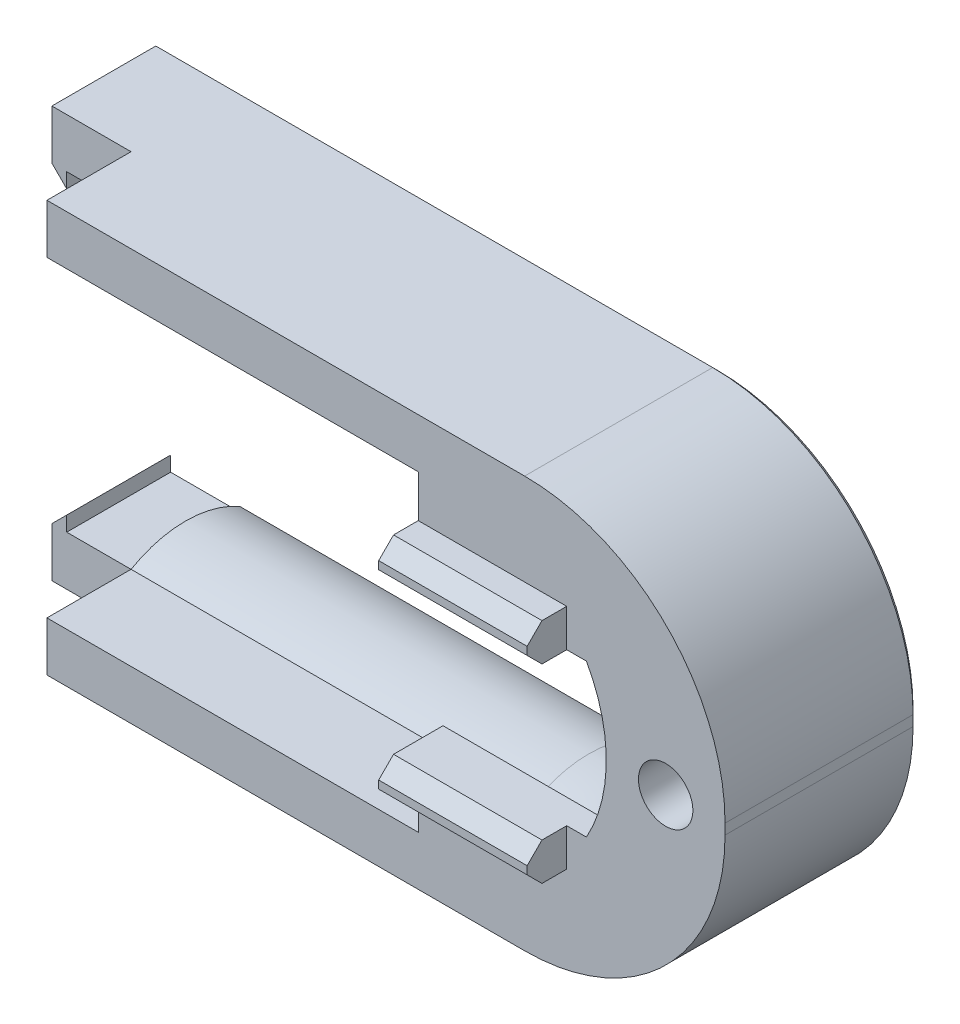
SolidWorks part; units mm, degrees
ref_plane "Top" through (0, 0, 0) normal (0, 0, 1) x (1, 0, 0)
ref_plane "Front" through (0, 0, 0) normal (0, 1, 0) x (1, 0, 0)
ref_plane "Right" through (0, 0, 0) normal (1, 0, 0) x (0, 0, -1)
sketch "Sketch1" plane through (0, 0, 0) normal (0, 0, 1) x (1, 0, 0)
  line L0 (0, 0) -> (40.75, 0)
  line L1 (40.75, 28.6) -> (0, 28.6)
  arc A0 (40.75, 0) -> (40.75, 28.6) centre (40.75, 14.3) ccw
  dimension "D1" = 28.6
  dimension "D2" = 40.75
sketch "Sketch2" plane through (0, 0, 0) normal (1, 0, 0) x (0, 0, -1)
  line L4 (-5.5, -1.4737) -> (5.5, -1.4737)
  arc A2 (-5.5, -1.4737) -> (5.5, -1.4737) centre (0, -11) cw
  dimension "D1" = 11
  dimension "D2" = 11
  dimension "D3" = 5.5
sweep "Sweep1" add profiles "Sketch2" path "Sketch1"
sketch "Sketch3" plane through (0, 0, 0) normal (0, 0, 1) x (1, 0, 0)
  line L0 (0, 30.0737) -> (0, 35.0737)
  line L1 (0, 35.0737) -> (48.2737, 35.0737)
  line L2 (68.5237, 14.8237) -> (68.5237, 13.7763)
  line L3 (48.2737, -6.4737) -> (0, -6.4737)
  line L4 (0, -6.4737) -> (0, -1.4737)
  line L5 (0, 30.0737) -> (40.75, 30.0737)
  line L6 (0, -1.4737) -> (40.75, -1.4737)
  line L7 (0, -1.4737) -> (40.75, -1.4737) construction
  arc A0 (40.75, -1.4737) -> (40.75, 30.0737) centre (40.75, 14.3) ccw construction
  arc A1 (40.75, 30.0737) -> (40.75, -1.4737) centre (40.75, 14.3) cw
  arc A2 (48.2737, -6.4737) -> (68.5237, 13.7763) centre (48.2737, 13.7763) ccw
  arc A3 (68.5237, 14.8237) -> (48.2737, 35.0737) centre (48.2737, 14.8237) ccw
  circle A4 centre (62.5237, 14.3) radius 2.75
  point P18 (56.5237, 14.3)
  dimension "D3" = 20.25
  dimension "D4" = 5.5
  dimension "D5" = 6
  dimension "D1" = 5
  dimension "D2" = 12
extrude "Boss-Extrude1" add sketch "Sketch3" along normal blind 14 and the other way blind 5.5
sketch "Sketch10" plane through (0, 0, 14) normal (0, 0, 1) x (1, 0, 0)
  line L0 (0, 30.0737) -> (40.75, 30.0737) construction
  line L1 (33.5237, 30.0737) -> (56.5237, 30.0737)
  line L2 (33.5237, 30.0737) -> (33.5237, -1.4737)
  line L3 (33.5237, -1.4737) -> (56.5237, -1.4737)
  line L4 (56.5237, 30.0737) -> (56.5237, -1.4737)
  line L5 (0, -1.4737) -> (40.75, -1.4737) construction
  arc A0 (40.75, -1.4737) -> (40.75, 30.0737) centre (40.75, 14.3) ccw construction
  dimension "D1" = 23
extrude "Boss-Extrude2" add sketch "Sketch10" against normal blind 4.5
hole_wizard "CBORE for M5 Hex Socket Head Cap Screw2" positions "Sketch8" profile "Sketch9" counterbore size "M5" standard "DIN" end condition through all
sketch "Sketch8" plane through (0, 0, -5.5) normal (0, 0, -1) x (-1, 0, 0)
  point P0 (-62.5237, 14.3)
sketch "Sketch9" plane through (62.5237, 14.3, -5.5) normal (1, 0, 0) x (0, 1, 0)
  line L0 (0, 0) -> (0, 19.5)
  line L1 (0, 19.5) -> (2.75, 19.5)
  line L3 (2.75, 19.5) -> (2.75, 5.4)
  line L4 (2.75, 5.4) -> (5, 5.4)
  line L5 (5, 5.4) -> (5, 0)
  line L7 (5, 0) -> (0, 0)
  line L11 (0, -6.35) -> (0, 107.95) construction
  dimension "Thru Hole Dia." = 5.5
  dimension "Thru Hole Depth" = 19.5
  dimension "C'Bore Dia." = 10
  dimension "C'Bore Depth" = 5.4
sketch "Sketch11" plane through (0, 0, 14) normal (0, 0, 1) x (1, 0, 0)
  line L1 (37.5237, 25.8) -> (52.5237, 25.8)
  line L2 (37.5237, 25.8) -> (37.5237, 22)
  line L3 (37.5237, 22) -> (52.5237, 22)
  line L4 (52.5237, 25.8) -> (52.5237, 22)
  line L5 (37.5237, 6.6) -> (52.5237, 6.6)
  line L6 (37.5237, 6.6) -> (37.5237, 2.8)
  line L7 (37.5237, 2.8) -> (52.5237, 2.8)
  line L8 (52.5237, 6.6) -> (52.5237, 2.8)
  circle A0 centre (62.5237, 14.3) radius 2.75 construction
  dimension "D1" = 10
  dimension "D2" = 15
  dimension "D3" = 3.8
  dimension "D4" = 15.4
  dimension "D5" = 7.7
extrude "Boss-Extrude3" add sketch "Sketch11" along normal blind 4
chamfer "Chamfer1" distance 1.5 angle 45 4 edges at (45.0237, 25.8, 18) (45.0237, 22, 18) (45.0237, 6.6, 18) (45.0237, 2.8, 18)
sketch "Sketch12" plane through (0, 0, 14) normal (0, 0, 1) x (1, 0, 0)
  line L0 (0, -1.4737) -> (40.75, -1.4737) construction
  line L1 (33.5237, 30.0737) -> (37.5237, 30.0737)
  line L2 (33.5237, 30.0737) -> (33.5237, -1.4737)
  line L3 (33.5237, -1.4737) -> (37.5237, -1.4737)
  line L4 (37.5237, 30.0737) -> (37.5237, -1.4737)
  line L5 (37.5237, 25.8) -> (37.5237, 22) construction
extrude "Cut-Extrude1" cut sketch "Sketch12" against normal up to surface (4.5 mm away) up to face at (41.0803, 14.3, 9.5)
sketch "Sketch13" plane through (0, 0, 14) normal (0, 0, 1) x (1, 0, 0)
  line L1 (37.5237, 22) -> (52.5237, 22)
  line L2 (37.5237, 22) -> (37.5237, 6.6)
  line L3 (37.5237, 6.6) -> (52.5237, 6.6)
  line L4 (52.5237, 22) -> (52.5237, 6.6)
extrude "Cut-Extrude2" cut sketch "Sketch13" against normal up to surface (4.5 mm away) up to face at (43.0803, 14.3, 9.5)
sketch "Sketch14" plane through (0, 0, 9.5) normal (0, 0, -1) x (-1, 0, 0)
  line L0 (-52.5237, 22) -> (-54.5166, 22)
  line L1 (-52.5237, 22) -> (-52.5237, 6.6)
  line L2 (-52.5237, 6.6) -> (-54.5166, 6.6)
  arc A0 (-40.75, 30.0737) -> (-40.75, -1.4737) centre (-40.75, 14.3) ccw construction
  arc A1 (-54.5166, 22) -> (-54.5166, 6.6) centre (-40.75, 14.3) ccw
extrude "Cut-Extrude3" cut sketch "Sketch14" against normal up to surface (4.5 mm away) up to face at (37.6358, 14.3, 14)
chamfer "Chamfer2" distance 2 angle 75 4 edges at (46.0202, 6.6, 9.5) (37.5237, 2.5631, 9.5) (37.5237, 26.0369, 9.5) (46.0202, 22, 9.5) first distance on face at (48.188, 6.6, 13.3333) first distance on face at (37.5237, 3.1566, 14.5) first distance on face at (37.5237, 25.4434, 14.5) first distance on face at (48.188, 22, 13.3333)
sketch "Sketch15" plane through (0, 0, 0) normal (-1, 0, 0) x (0, 0, 1)
  line L1 (5.5, 30.0737) -> (-5.5, 30.0737)
  line L2 (5.5, 30.0737) -> (5.5, 35.0737)
  line L3 (5.5, 35.0737) -> (-5.5, 35.0737)
  line L4 (-5.5, 30.0737) -> (-5.5, 35.0737)
extrude "Boss-Extrude4" add sketch "Sketch15" along normal blind 8
sketch "Sketch16" plane through (0, 0, -5.5) normal (0, 0, -1) x (-1, 0, 0)
  line L2 (8, 30.0737) -> (0, 30.0737) construction
  line L3 (6.5, 30.0737) -> (8, 30.0737)
  line L4 (8, 30.0737) -> (8, 28.0737)
  line L5 (8, 28.0737) -> (6.5, 28.0737)
  line L6 (6.5, 28.0737) -> (6.5, 30.0737)
  dimension "D1" = 6.5
  dimension "D2" = 2
extrude "Boss-Extrude5" add sketch "Sketch16" against normal up to surface (11 mm away) up to face at (-4, 32.5737, 5.5)
ref_plane "Plane1" through (0, 14.3, 0) normal (0, -1, 0) x (-1, 0, 0)
mirror "Mirror1" about plane through (0, 14.3, 0) normal (0, -1, 0) of "Boss-Extrude5", "Boss-Extrude4"
chamfer "Chamfer4" distance 2 angle 45 2 edges at (-8, 28.0737, 0) (-8, 0.5263, 0)
chamfer "Chamfer3" distance 0.5 angle 45 14 edges at (57.5237, 14.3, -5.5) (20.1369, -6.4737, -5.5) (62.5926, -0.5426, -5.5) (68.5237, 14.3, -5.5) (62.5926, 29.1426, -5.5) (20.1369, 35.0737, -5.5) (-3.25, -1.4737, -5.5) (-6.5, -0.7237, -5.5) (-7.25, -0.7237, -5.5) (-8, -3.9737, -5.5) (-3.25, 30.0737, -5.5) (-6.5, 29.3237, -5.5) (-7.25, 29.3237, -5.5) (-8, 32.5737, -5.5)
